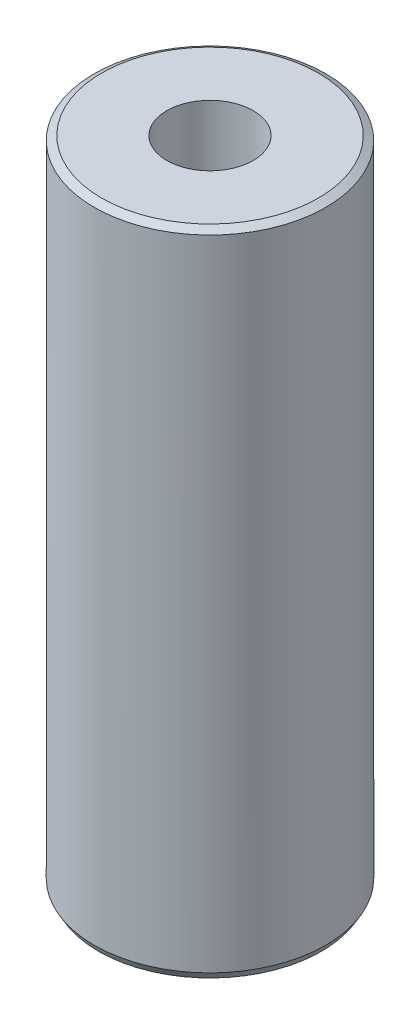
SolidWorks part; units mm, degrees
ref_plane "Front Plane" through (0, 0, 0) normal (0, 0, 1) x (1, 0, 0)
ref_plane "Top Plane" through (0, 0, 0) normal (0, 1, 0) x (1, 0, 0)
ref_plane "Right Plane" through (0, 0, 0) normal (1, 0, 0) x (0, 0, -1)
sketch "Sketch1" plane through (0, 0, 0) normal (0, 1, 0) x (1, 0, 0)
  circle A0 centre (0, 0) radius 37.5
  dimension "SHAFT_OD" = 75
extrude "Boss-Extrude1" add sketch "Sketch1" along normal blind 210.7547
sketch "Sketch2" plane through (0, 0, 0) normal (0, 1, 0) x (1, 0, 0)
  circle A0 centre (0, 0) radius 13.9963
  dimension "BORE_D" = 27.9926
extrude "Cut-Extrude1" cut sketch "Sketch2" along normal through all
chamfer "Chamfer1" distance 1.3922 angle 60 2 edges at (0, 210.7547, 37.5) (0, 0, 37.5) first distance on face at (0, 210.7547, 37.5) first distance on face at (0, 0, 13.9963)
